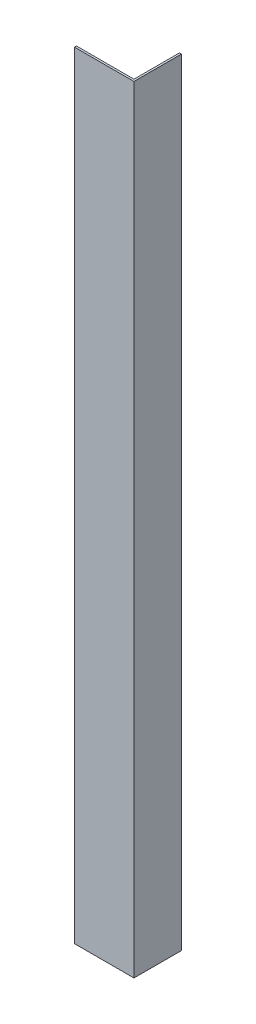
SolidWorks part; units mm, degrees
material "6061-T6 (SS)"
ref_plane "Alzado" through (0, 0, 0) normal (0, 0, 1) x (1, 0, 0)
ref_plane "Planta" through (0, 0, 0) normal (0, 1, 0) x (1, 0, 0)
ref_plane "Vista lateral" through (0, 0, 0) normal (1, 0, 0) x (0, 0, -1)
sketch "Sketch1" plane through (0, 0, 0) normal (0, 1, 0) x (1, 0, 0)
  line L0 (0, 0) -> (15, 0)
  line L1 (15, 0) -> (15, 12)
  line L2 (15, 12) -> (14.5, 12)
  line L3 (14.5, 12) -> (14.5, 0.5)
  line L4 (14.5, 0.5) -> (0, 0.5)
  line L5 (0, 0.5) -> (0, 0)
  dimension "D1" = 15
  dimension "D2" = 12
  dimension "D3" = 0.5
  dimension "D4" = 0.5
extrude "Boss-Extrude1" add sketch "Sketch1" along normal blind 196
